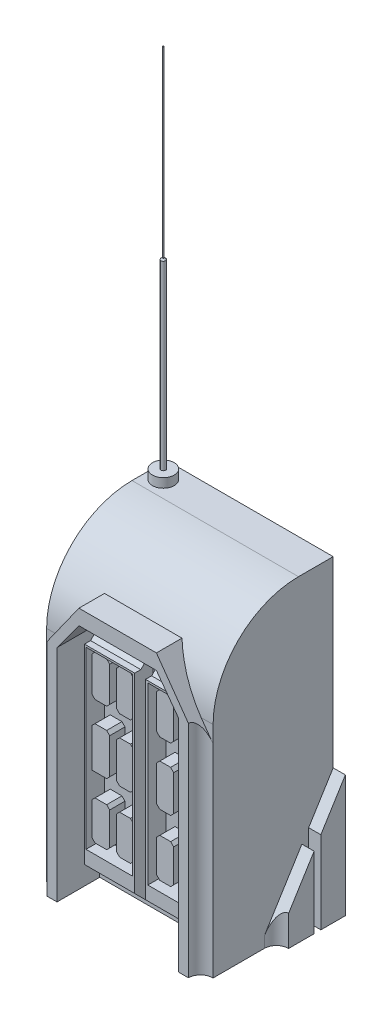
SolidWorks part; units mm, degrees
note: The reader was unsure of these and kept them because the rebuilt part matched: shared geometry of "Sketch2<3>", "Sketch2<5>".
ref_plane "Front Plane" through (0, 0, 0) normal (0, 0, 1) x (1, 0, 0)
ref_plane "Top Plane" through (0, 0, 0) normal (0, 1, 0) x (1, 0, 0)
ref_plane "Right Plane" through (0, 0, 0) normal (1, 0, 0) x (0, 0, -1)
sketch "Sketch1" plane through (0, 0, 0) normal (0, 1, 0) x (1, 0, 0)
  line L1 (-67.7347, 47.2632) -> (70.9691, 47.2632)
  line L2 (-67.7347, 47.2632) -> (-67.7347, -52.7743)
  line L3 (-67.7347, -52.7743) -> (70.9691, -52.7743)
  line L4 (70.9691, 47.2632) -> (70.9691, -52.7743)
extrude "Boss-Extrude1" add sketch "Sketch1" along normal blind 254
sketch "Sketch2" plane through (0, 0, 52.7743) normal (0, 0, 1) x (1, 0, 0)
  line L0 (-57.3228, 0) -> (-57.3228, 183.5787)
  line L1 (-67.7347, 0) -> (70.9691, 0) construction
  line L2 (-57.3228, 183.5787) -> (-30.6598, 221.102)
  line L3 (-30.6598, 221.102) -> (33.8942, 221.102)
  line L4 (-48.9078, 0) -> (-48.9078, 183.5787)
  line L5 (60.5573, 0) -> (-57.3228, 0)
  line L6 (60.5573, 183.5787) -> (33.8942, 221.102)
  line L7 (60.5573, 0) -> (60.5573, 183.5787)
  line L8 (-48.9078, 183.5787) -> (-30.6598, 208.4574)
  line L9 (-30.6598, 208.4574) -> (33.8942, 208.4574)
  line L11 (-42.6728, 173.1416) -> (-42.6728, 139.0376)
  line L12 (-42.6728, 173.1416) -> (-27.8716, 173.1416)
  line L13 (-8.053, 173.1416) -> (-8.053, 139.0376)
  line L14 (-8.053, 139.0376) -> (-22.1883, 139.0376)
  line L15 (-42.6728, 121.606) -> (-27.8716, 121.606)
  line L16 (-8.053, 121.606) -> (-8.053, 86.8336)
  line L17 (-8.053, 86.8336) -> (-22.1883, 86.8336)
  line L18 (-42.6728, 86.8336) -> (-42.6728, 121.606)
  line L19 (-42.6728, 68.0098) -> (-27.8716, 68.0098)
  line L20 (-8.053, 68.0098) -> (-8.053, 35.5359)
  line L21 (-8.053, 35.5359) -> (-22.1883, 35.5359)
  line L22 (-42.6728, 35.5359) -> (-42.6728, 68.0098)
  line L23 (-27.8716, 173.1416) -> (-27.8716, 139.0376)
  line L24 (-22.1883, 68.0098) -> (-8.053, 68.0098)
  line L25 (-22.1883, 139.0376) -> (-22.1883, 173.1416)
  line L26 (-27.8716, 121.606) -> (-27.8716, 86.8336)
  line L27 (31.1061, 139.0376) -> (45.9072, 139.0376)
  line L28 (-22.1883, 86.8336) -> (-22.1883, 121.606)
  line L29 (-27.8716, 68.0098) -> (-27.8716, 35.5359)
  line L30 (52.1423, 183.5787) -> (33.8942, 208.4574)
  line L31 (-22.1883, 35.5359) -> (-22.1883, 68.0098)
  line L32 (-22.1883, 173.1416) -> (-8.053, 173.1416)
  line L33 (-27.8716, 139.0376) -> (-42.6728, 139.0376)
  line L34 (-22.1883, 121.606) -> (-8.053, 121.606)
  line L35 (-27.8716, 86.8336) -> (-42.6728, 86.8336)
  line L36 (-27.8716, 35.5359) -> (-42.6728, 35.5359)
  line L37 (11.2875, 139.0376) -> (25.4228, 139.0376)
  line L38 (11.2875, 173.1416) -> (11.2875, 139.0376)
  line L39 (25.4228, 173.1416) -> (11.2875, 173.1416)
  line L40 (25.4228, 139.0376) -> (25.4228, 173.1416)
  line L41 (31.1061, 173.1416) -> (31.1061, 139.0376)
  line L42 (45.9072, 173.1416) -> (31.1061, 173.1416)
  line L43 (45.9072, 173.1416) -> (45.9072, 139.0376)
  line L44 (31.1061, 86.8336) -> (45.9072, 86.8336)
  line L45 (45.9072, 86.8336) -> (45.9072, 121.606)
  line L46 (45.9072, 121.606) -> (31.1061, 121.606)
  line L47 (31.1061, 121.606) -> (31.1061, 86.8336)
  line L48 (25.4228, 86.8336) -> (25.4228, 121.606)
  line L49 (25.4228, 121.606) -> (11.2875, 121.606)
  line L50 (11.2875, 121.606) -> (11.2875, 86.8336)
  line L51 (11.2875, 86.8336) -> (25.4228, 86.8336)
  line L52 (11.2875, 68.0098) -> (11.2875, 35.5359)
  line L53 (25.4228, 68.0098) -> (11.2875, 68.0098)
  line L54 (25.4228, 35.5359) -> (25.4228, 68.0098)
  line L55 (31.1061, 68.0098) -> (31.1061, 35.5359)
  line L56 (11.2875, 35.5359) -> (25.4228, 35.5359)
  line L57 (31.1061, 35.5359) -> (45.9072, 35.5359)
  line L58 (45.9072, 68.0098) -> (31.1061, 68.0098)
  line L59 (45.9072, 35.5359) -> (45.9072, 68.0098)
  line L60 (52.1423, 0) -> (52.1423, 183.5787)
  line M1 (-67.7347, 0) -> (70.9691, 0)
extrude "Cut-Extrude1" cut sketch "Sketch2" against normal blind 25.4
extrude "Cut-Extrude2" cut sketch "Sketch2<3>" against normal blind 12.7 contours L33 L23 L12 L11 | L32 L25 L14 L13 | L35 L26 L15 L18 | L34 L28 L17 L16 | L36 L29 L19 L22 | L31 L21 L20 L24 | L37 L40 L39 L38 | L43 L42 L41 L27 | L46 L47 L44 L45 | L50 L51 L48 L49 | L52 L56 L54 L53 | L57 L59 L58 L55
sketch "Sketch2<3>" plane through (0, 0, 52.7743) normal (0, 0, 1) x (1, 0, 0) same geometry as "Sketch2"
extrude "Boss-Extrude2" add sketch "Sketch2<5>" along normal blind 10.16 contours L60 L5 L7 L6 L3 L2 L0 L4 L8 L9 L30 M1
sketch "Sketch2<5>" plane through (0, 0, 52.7743) normal (0, 0, 1) x (1, 0, 0) same geometry as "Sketch2"
fillet "Fillet1" radius 71.12 1 edges at (1.6172, 254, 52.7743)
chamfer "Chamfer1" distance 2.54 angle 45 47 edges at (-42.6728, 121.606, 33.7243) (-22.1883, 121.606, 33.7243) (-27.8716, 121.606, 33.7243) (-8.053, 121.606, 33.7243) (11.2875, 121.606, 33.7243) (25.4228, 121.606, 33.7243) (45.9072, 121.606, 33.7243) (31.1061, 121.606, 33.7243) (45.9072, 68.0098, 33.7243) (31.1061, 68.0098, 33.7243) (25.4228, 68.0098, 33.7243) (11.2875, 68.0098, 33.7243) (-8.053, 68.0098, 33.7243) (-22.1883, 68.0098, 33.7243) (-42.6728, 68.0098, 33.7243) (-27.8716, 68.0098, 33.7243) (-42.6728, 35.5359, 33.7243) (-27.8716, 35.5359, 33.7243) (-22.1883, 35.5359, 33.7243) (-8.053, 35.5359, 33.7243) (45.9072, 35.5359, 33.7243) (31.1061, 35.5359, 33.7243) (25.4228, 35.5359, 33.7243) (11.2875, 35.5359, 33.7243) (45.9072, 86.8336, 33.7243) (31.1061, 86.8336, 33.7243) (25.4228, 86.8336, 33.7243) (11.2875, 86.8336, 33.7243) (-8.053, 86.8336, 33.7243) (-27.8716, 86.8336, 33.7243) (-22.1883, 86.8336, 33.7243) (-42.6728, 139.0376, 33.7243) (45.9072, 139.0376, 33.7243) (31.1061, 139.0376, 33.7243) (25.4228, 139.0376, 33.7243) (11.2875, 139.0376, 33.7243) (-22.1883, 139.0376, 33.7243) (45.9072, 173.1416, 33.7243) (31.1061, 173.1416, 33.7243) (11.2875, 173.1416, 33.7243) (25.4228, 173.1416, 33.7243) (-8.053, 139.0376, 33.7243) (-27.8716, 139.0376, 33.7243) (-42.6728, 173.1416, 33.7243) (-22.1883, 173.1416, 33.7243) (-8.053, 173.1416, 33.7243) (-27.8716, 173.1416, 33.7243)
sketch "Sketch3" plane through (0, 0, 27.3743) normal (0, 0, 1) x (1, 0, 0)
  line L0 (0, 186.3982) -> (0, 140.7668)
  line L1 (-45.0899, 175.5674) -> (-45.0899, 29.7272)
  line L3 (-4.5044, 177.1474) -> (-4.5044, 28.3126)
  line L4 (-4.5044, 28.3126) -> (-46.3541, 28.3126)
  line L5 (-46.3541, 28.3126) -> (-46.3541, 177.1474)
  line L6 (-45.0899, 29.7272) -> (-6.4298, 29.7272)
  line L7 (-6.4298, 29.7272) -> (-6.4298, 175.5674)
  line L8 (-6.4298, 175.5674) -> (-45.0899, 175.5674)
  line L9 (-4.5044, 177.1474) -> (-46.3541, 177.1474)
  line L10 (45.0899, 29.7272) -> (6.4298, 29.7272)
  line L11 (4.5044, 28.3126) -> (46.3541, 28.3126)
  line L12 (4.5044, 177.1474) -> (46.3541, 177.1474)
  line L13 (6.4298, 175.5674) -> (45.0899, 175.5674)
  line L14 (6.4298, 29.7272) -> (6.4298, 175.5674)
  line L15 (4.5044, 177.1474) -> (4.5044, 28.3126)
  line L16 (46.3541, 28.3126) -> (46.3541, 177.1474)
  line L17 (45.0899, 175.5674) -> (45.0899, 29.7272)
extrude "Boss-Extrude3" add sketch "Sketch3" along normal blind 15.24 contours L3 L9 L5 L4 L8 L7 L6 L1 | L11 L16 L12 L15 L13 L17 L10 L14
sketch "Sketch4" plane through (-67.7347, 0, 0) normal (-1, 0, 0) x (0, 0, 1)
  line L0 (-47.2632, 0) -> (-26.326, 0)
  line L1 (0, 0) -> (0, 25.4)
  line L2 (-47.2632, 0) -> (-47.2632, 101.6)
  line L3 (-47.2632, 254) -> (-47.2632, 0) construction
  line L4 (-47.2632, 101.6) -> (-26.326, 67.844)
  line L5 (-20.6226, 58.6488) -> (0, 25.4)
  line L6 (-26.326, 67.844) -> (-26.326, 0)
  line L8 (-20.6226, 0) -> (-20.6226, 58.6488)
  line L9 (-20.6226, 0) -> (0, 0)
extrude "Boss-Extrude4" add sketch "Sketch4" along normal blind 10.16
sketch "Sketch5" plane through (70.9691, 0, 0) normal (1, 0, 0) x (0, 0, -1)
  line L0 (0, 0) -> (0, 25.4)
  line L1 (0, 25.4) -> (21.2139, 59.6021)
  line L2 (47.2632, 254) -> (47.2632, 0) construction
  line L3 (47.2632, 101.6) -> (47.2632, 0)
  line L4 (47.2632, 0) -> (26.8291, 0)
  line L5 (26.8291, 68.6552) -> (47.2632, 101.6)
  line L6 (21.2139, 59.6021) -> (21.2139, 0)
  line L8 (26.8291, 0) -> (26.8291, 68.6552)
  line L9 (21.2139, 0) -> (0, 0)
extrude "Boss-Extrude5" add sketch "Sketch5" along normal blind 10.16
sketch "Sketch6" plane through (0, 254, 0) normal (0, 1, 0) x (1, 0, 0)
  circle A0 centre (-55.4865, 32.2211) radius 9.0271
extrude "Boss-Extrude6" add sketch "Sketch6" along normal blind 7.62
sketch "Sketch7" plane through (0, 261.62, 0) normal (0, 1, 0) x (1, 0, 0)
  circle A0 centre (-55.4865, 32.2211) radius 1.9404
extrude "Boss-Extrude7" add sketch "Sketch7" along normal blind 152.4
chamfer "Chamfer2" distance 1.27 angle 45 1 edges at (-55.4865, 414.02, -30.2807)
sketch "Sketch8" plane through (0, 414.02, 0) normal (0, 1, 0) x (1, 0, 0)
  circle A0 centre (-55.4865, 32.2211) radius 0.4223
extrude "Boss-Extrude8" add sketch "Sketch8" along normal blind 152.4
fillet "Fillet2" radius 10.16 1 edges
fillet "Fillet3" radius 10.16 1 edges
chamfer "Chamfer3" distance 25.4 angle 45 2 edges at (-25.4292, 28.3126, 27.3743) (25.4292, 28.3126, 27.3743)
chamfer "Chamfer4" distance 10.16 angle 45 2 edges at (25.4292, 177.1474, 27.3743) (-25.4292, 177.1474, 27.3743)
fillet "Fillet4" radius 10.16 1 edges at (-67.7347, 12.7, 0)
fillet "Fillet5" radius 10.16 1 edges
